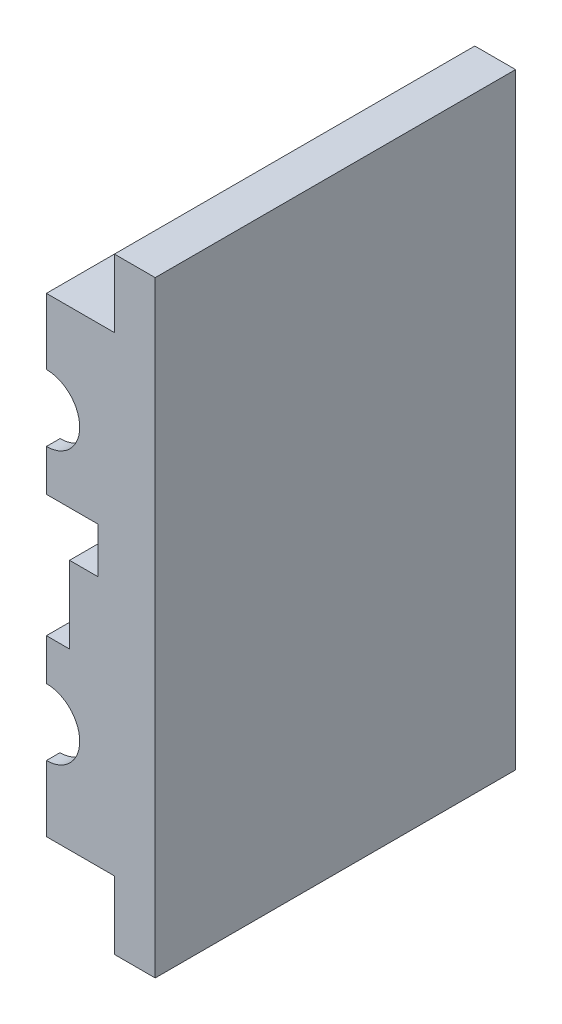
SolidWorks part; units mm, degrees
ref_plane "Front Plane" through (0, 0, 0) normal (0, 0, 1) x (1, 0, 0)
ref_plane "Top Plane" through (0, 0, 0) normal (0, 1, 0) x (1, 0, 0)
ref_plane "Right Plane" through (0, 0, 0) normal (1, 0, 0) x (0, 0, -1)
sketch "Sketch1" plane through (0, 0, 0) normal (0, 0, 1) x (1, 0, 0)
  line L0 (0, 0) -> (0, -89.2)
  line L1 (0, -89.2) -> (-6, -89.2)
  line L2 (-6, -89.2) -> (-6, -79.2)
  line L3 (-6, -79.2) -> (-16, -79.2)
  line L4 (-16, -79.2) -> (-16, -72.2)
  line L5 (-16, -57) -> (-16, -42.3)
  line L6 (-16, -42.3) -> (-8.4, -42.3)
  line L7 (-8.4, -42.3) -> (-8.4, -35.6)
  line L8 (-8.4, -35.6) -> (-16, -35.6)
  line L9 (-16, -35.6) -> (-16, -32.2)
  line L10 (-16, -17) -> (-16, -10)
  line L11 (-16, -10) -> (-6, -10)
  line L12 (-6, -10) -> (-6, 0)
  line L13 (-6, 0) -> (0, 0)
  arc A0 (-16, -72.2) -> (-16, -57) centre (-16, -64.6) ccw
  arc A1 (-16, -32.2) -> (-16, -17) centre (-16, -24.6) ccw
  dimension "D6" = 7.6
  dimension "D7" = 7.6
  dimension "D1" = 6
  dimension "D2" = 10
  dimension "D3" = 10
  dimension "D4" = 14.7
  dimension "D5" = 40
  dimension "D8" = 7
  dimension "D9" = 3.4
  dimension "D11" = 10
  dimension "D12" = 10
extrude "Boss-Extrude1" add sketch "Sketch1" along normal blind 53
ref_plane "Plane1" through (0, 0, 26.5) normal (0, 0, -1) x (-1, 0, 0)
sketch "Sketch2" plane through (0, 0, 26.5) normal (0, 0, -1) x (-1, 0, 0)
  line L0 (16, -32.2) -> (16, -29.5)
  line L1 (16, -19.7) -> (16, -17)
  arc A0 (16, -17) -> (16, -32.2) centre (16, -24.6) ccw
  arc A1 (16, -19.7) -> (16, -29.5) centre (16, -24.6) ccw
  dimension "D1" = 4.9
extrude "Boss-Extrude2" add sketch "Sketch2" along normal blind 2
sketch "Sketch3" plane through (0, 0, 26.5) normal (0, 0, -1) x (-1, 0, 0)
  line L0 (16, -72.2) -> (16, -69.5)
  line L1 (16, -59.7) -> (16, -57)
  arc A0 (16, -57) -> (16, -72.2) centre (16, -64.6) ccw
  arc A1 (16, -59.7) -> (16, -69.5) centre (16, -64.6) ccw
  dimension "D1" = 4.9
extrude "Boss-Extrude3" add sketch "Sketch3" along normal blind 2
ref_plane "Plane2" through (0, 0, 2) normal (0, 0, -1) x (-1, 0, 0)
sketch "Sketch4" plane through (0, 0, 2) normal (0, 0, -1) x (-1, 0, 0)
  line L1 (16, -57) -> (16, -59.7)
  line L2 (16, -72.2) -> (16, -79.2) construction
  line L4 (16, -69.5) -> (16, -72.2)
  line L5 (16, -17) -> (16, -19.7)
  line L6 (16, -29.5) -> (16, -32.2)
  arc A1 (16, -57) -> (16, -72.2) centre (16, -64.6) ccw construction
  arc A2 (16, -72.2) -> (16, -57) centre (16, -64.6) cw
  arc A4 (16, -59.7) -> (16, -69.5) centre (16, -64.6) ccw
  arc A5 (16, -32.2) -> (16, -17) centre (16, -24.6) cw
  arc A6 (16, -19.7) -> (16, -29.5) centre (16, -24.6) ccw
  dimension "D1" = 4.9
  dimension "D2" = 4.9
extrude "Boss-Extrude5" add sketch "Sketch4" along normal blind 2
ref_plane "Plane3" through (0, 0, 51) normal (0, 0, -1) x (-1, 0, 0)
sketch "Sketch5" plane through (0, 0, 51) normal (0, 0, -1) x (-1, 0, 0)
  line L0 (16, -17) -> (16, -19.7)
  line L1 (16, -29.5) -> (16, -32.2)
  line L2 (16, -57) -> (16, -59.7)
  line L3 (16, -69.5) -> (16, -72.2)
  arc A0 (16, -17) -> (16, -32.2) centre (16, -24.6) ccw construction
  arc A1 (16, -32.2) -> (16, -17) centre (16, -24.6) cw
  arc A2 (16, -19.7) -> (16, -29.5) centre (16, -24.6) ccw
  arc A3 (16, -72.2) -> (16, -57) centre (16, -64.6) cw
  arc A4 (16, -59.7) -> (16, -69.5) centre (16, -64.6) ccw
  dimension "D1" = 4.9
extrude "Boss-Extrude6" add sketch "Sketch5" against normal blind 2
sketch "Sketch7" plane through (0, 0, 53) normal (0, 0, 1) x (1, 0, 0)
  line L1 (-16, -42.3) -> (-12.6, -42.3)
  line L2 (-16, -42.3) -> (-16, -53.6)
  line L3 (-16, -53.6) -> (-12.6, -53.6)
  line L4 (-12.6, -42.3) -> (-12.6, -53.6)
  dimension "D1" = 3.4
  dimension "D2" = 11.3
extrude "Cut-Extrude2" cut sketch "Sketch7" against normal up to surface (53 mm away) up to face at (-9.9375, -43.1875, 0)
